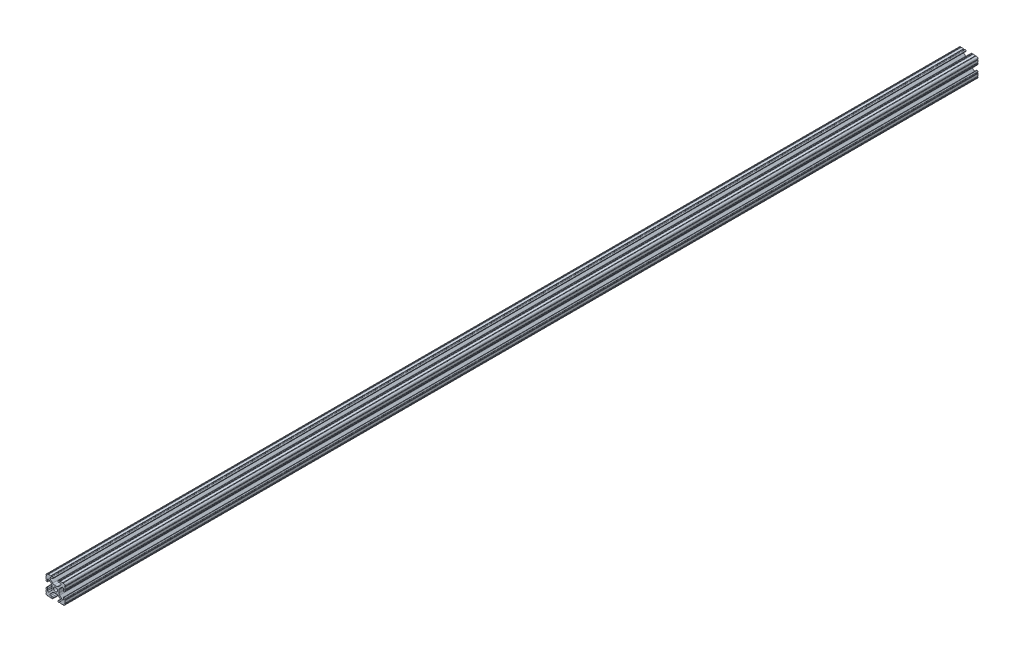
SolidWorks part; units mm, degrees
ref_plane "Front Plane" through (0, 0, 0) normal (0, 0, 1) x (1, 0, 0)
ref_plane "Top Plane" through (0, 0, 0) normal (0, 1, 0) x (1, 0, 0)
ref_plane "Right Plane" through (0, 0, 0) normal (1, 0, 0) x (0, 0, -1)
sketch "Sketch1" plane through (0, 0, 0) normal (0, 0, 1) x (1, 0, 0)
  line L88 (-7.1797, -8.6452) -> (-3.9523, -5.4237)
  line L89 (-1.7093, -4.4958) -> (1.7093, -4.4958)
  line L90 (3.9523, -5.4237) -> (7.1797, -8.6452)
  line L91 (6.4164, -10.4902) -> (4.2875, -10.4902)
  line L92 (3.2385, -11.5392) -> (3.2385, -11.651)
  line L93 (4.2875, -12.7) -> (5.3171, -12.7)
  line L94 (6.3331, -12.7) -> (9.5504, -12.7)
  line L95 (12.7, -9.5504) -> (12.7, -6.3331)
  line L96 (12.7, -5.3171) -> (12.7, -4.2875)
  line L97 (11.651, -3.2385) -> (11.5392, -3.2385)
  line L98 (10.4902, -4.2875) -> (10.4902, -6.4021)
  line L99 (8.7371, -7.1294) -> (5.441, -3.8408)
  line L100 (4.5085, -1.5932) -> (4.5085, 1.5932)
  line L101 (5.441, 3.8408) -> (8.7371, 7.1294)
  line L102 (10.4902, 6.4021) -> (10.4902, 4.2875)
  line L103 (11.5392, 3.2385) -> (11.651, 3.2385)
  line L104 (12.7, 4.2875) -> (12.7, 5.3171)
  line L105 (12.7, 6.3331) -> (12.7, 9.5504)
  line L106 (9.5504, 12.7) -> (6.3331, 12.7)
  line L107 (5.3171, 12.7) -> (4.2875, 12.7)
  line L108 (3.2385, 11.651) -> (3.2385, 11.5392)
  line L109 (4.2875, 10.4902) -> (6.4768, 10.4902)
  line L110 (7.207, 8.7244) -> (3.8983, 5.4232)
  line L111 (1.6558, 4.4958) -> (-1.6558, 4.4958)
  line L112 (-3.8983, 5.4232) -> (-7.207, 8.7244)
  line L113 (-6.4768, 10.4902) -> (-4.2875, 10.4902)
  line L114 (-3.2385, 11.5392) -> (-3.2385, 11.651)
  line L115 (-4.2875, 12.7) -> (-5.3171, 12.7)
  line L116 (-6.3331, 12.7) -> (-9.5504, 12.7)
  line L117 (-12.7, 9.5504) -> (-12.7, 6.3331)
  line L118 (-12.7, 5.3171) -> (-12.7, 4.2875)
  line L119 (-11.651, 3.2385) -> (-11.5392, 3.2385)
  line L120 (-10.4902, 4.2875) -> (-10.4902, 6.4021)
  line L121 (-8.7371, 7.1294) -> (-5.441, 3.8408)
  line L122 (-4.5085, 1.5932) -> (-4.5085, -1.5932)
  line L123 (-5.441, -3.8408) -> (-8.7371, -7.1294)
  line L124 (-10.4902, -6.4021) -> (-10.4902, -4.2875)
  line L125 (-11.5392, -3.2385) -> (-11.651, -3.2385)
  line L126 (-12.7, -4.2875) -> (-12.7, -5.3171)
  line L127 (-12.7, -6.3331) -> (-12.7, -9.5504)
  line L128 (-9.5504, -12.7) -> (-6.3331, -12.7)
  line L129 (-5.3171, -12.7) -> (-4.2875, -12.7)
  line L130 (-3.2385, -11.651) -> (-3.2385, -11.5392)
  line L131 (-4.2875, -10.4902) -> (-6.4164, -10.4902)
  circle A1 centre (0, 0) radius 2.6035
  arc A104 (-7.1797, -8.6452) -> (-6.4164, -10.4902) centre (-6.4164, -9.4098) ccw
  arc A105 (-1.7093, -4.4958) -> (-3.9523, -5.4237) centre (-1.7093, -7.6708) ccw
  arc A106 (3.9523, -5.4237) -> (1.7093, -4.4958) centre (1.7093, -7.6708) ccw
  arc A107 (6.4164, -10.4902) -> (7.1797, -8.6452) centre (6.4164, -9.4098) ccw
  arc A108 (4.2875, -10.4902) -> (3.2385, -11.5392) centre (4.2875, -11.5392) ccw
  arc A109 (3.2385, -11.651) -> (4.2875, -12.7) centre (4.2875, -11.651) ccw
  arc A110 (6.3331, -12.7) -> (5.3171, -12.7) centre (5.8251, -12.7) ccw
  arc A111 (10.5664, -12.6998) -> (9.5504, -12.7) centre (10.0584, -12.7) ccw
  arc A112 (10.5664, -12.6998) -> (12.6998, -10.5664) centre (10.5918, -10.5918) ccw
  arc A113 (12.7, -9.5504) -> (12.6998, -10.5664) centre (12.7, -10.0584) ccw
  arc A114 (12.7, -5.3171) -> (12.7, -6.3331) centre (12.7, -5.8251) ccw
  arc A115 (12.7, -4.2875) -> (11.651, -3.2385) centre (11.651, -4.2875) ccw
  arc A116 (11.5392, -3.2385) -> (10.4902, -4.2875) centre (11.5392, -4.2875) ccw
  arc A117 (8.7371, -7.1294) -> (10.4902, -6.4021) centre (9.4628, -6.4021) ccw
  arc A118 (4.5085, -1.5932) -> (5.441, -3.8408) centre (7.6835, -1.5932) ccw
  arc A119 (5.441, 3.8408) -> (4.5085, 1.5932) centre (7.6835, 1.5932) ccw
  arc A120 (10.4902, 6.4021) -> (8.7371, 7.1294) centre (9.4628, 6.4021) ccw
  arc A121 (10.4902, 4.2875) -> (11.5392, 3.2385) centre (11.5392, 4.2875) ccw
  arc A122 (11.651, 3.2385) -> (12.7, 4.2875) centre (11.651, 4.2875) ccw
  arc A123 (12.7, 6.3331) -> (12.7, 5.3171) centre (12.7, 5.8251) ccw
  arc A124 (12.6998, 10.5664) -> (12.7, 9.5504) centre (12.7, 10.0584) ccw
  arc A125 (12.6998, 10.5664) -> (10.5664, 12.6998) centre (10.5918, 10.5918) ccw
  arc A126 (9.5504, 12.7) -> (10.5664, 12.6998) centre (10.0584, 12.7) ccw
  arc A127 (5.3171, 12.7) -> (6.3331, 12.7) centre (5.8251, 12.7) ccw
  arc A128 (4.2875, 12.7) -> (3.2385, 11.651) centre (4.2875, 11.651) ccw
  arc A129 (3.2385, 11.5392) -> (4.2875, 10.4902) centre (4.2875, 11.5392) ccw
  arc A130 (7.207, 8.7244) -> (6.4768, 10.4902) centre (6.4768, 9.4563) ccw
  arc A131 (1.6558, 4.4958) -> (3.8983, 5.4232) centre (1.6558, 7.6708) ccw
  arc A132 (-3.8983, 5.4232) -> (-1.6558, 4.4958) centre (-1.6558, 7.6708) ccw
  arc A133 (-6.4768, 10.4902) -> (-7.207, 8.7244) centre (-6.4768, 9.4563) ccw
  arc A134 (-4.2875, 10.4902) -> (-3.2385, 11.5392) centre (-4.2875, 11.5392) ccw
  arc A135 (-3.2385, 11.651) -> (-4.2875, 12.7) centre (-4.2875, 11.651) ccw
  arc A136 (-6.3331, 12.7) -> (-5.3171, 12.7) centre (-5.8251, 12.7) ccw
  arc A137 (-10.5664, 12.6998) -> (-9.5504, 12.7) centre (-10.0584, 12.7) ccw
  arc A138 (-10.5664, 12.6998) -> (-12.6998, 10.5664) centre (-10.5918, 10.5918) ccw
  arc A139 (-12.7, 9.5504) -> (-12.6998, 10.5664) centre (-12.7, 10.0584) ccw
  arc A140 (-12.7, 5.3171) -> (-12.7, 6.3331) centre (-12.7, 5.8251) ccw
  arc A141 (-12.7, 4.2875) -> (-11.651, 3.2385) centre (-11.651, 4.2875) ccw
  arc A142 (-11.5392, 3.2385) -> (-10.4902, 4.2875) centre (-11.5392, 4.2875) ccw
  arc A143 (-8.7371, 7.1294) -> (-10.4902, 6.4021) centre (-9.4628, 6.4021) ccw
  arc A144 (-4.5085, 1.5932) -> (-5.441, 3.8408) centre (-7.6835, 1.5932) ccw
  arc A145 (-5.441, -3.8408) -> (-4.5085, -1.5932) centre (-7.6835, -1.5932) ccw
  arc A146 (-10.4902, -6.4021) -> (-8.7371, -7.1294) centre (-9.4628, -6.4021) ccw
  arc A147 (-10.4902, -4.2875) -> (-11.5392, -3.2385) centre (-11.5392, -4.2875) ccw
  arc A148 (-11.651, -3.2385) -> (-12.7, -4.2875) centre (-11.651, -4.2875) ccw
  arc A149 (-12.7, -6.3331) -> (-12.7, -5.3171) centre (-12.7, -5.8251) ccw
  arc A150 (-12.6998, -10.5664) -> (-12.7, -9.5504) centre (-12.7, -10.0584) ccw
  arc A151 (-12.6998, -10.5664) -> (-10.5664, -12.6998) centre (-10.5918, -10.5918) ccw
  arc A152 (-9.5504, -12.7) -> (-10.5664, -12.6998) centre (-10.0584, -12.7) ccw
  arc A153 (-5.3171, -12.7) -> (-6.3331, -12.7) centre (-5.8251, -12.7) ccw
  arc A154 (-4.2875, -12.7) -> (-3.2385, -11.651) centre (-4.2875, -11.651) ccw
  arc A155 (-3.2385, -11.5392) -> (-4.2875, -10.4902) centre (-4.2875, -11.5392) ccw
extrude "Boss-Extrude1" add sketch "Sketch1" along normal mid plane 1219.2
sketch "Sketch2" plane through (4.5085, 0, 0) normal (1, 0, 0) x (0, 0, -1)
  line L1 (0, 17.2111) -> (0, -17.5175) construction
  circle A0 centre (38.1, 0) radius 3.175
  circle A2 centre (-38.1, 0) radius 3.175
  circle A3 centre (0, 0) radius 3.175
  dimension "D1" = 6.35
  dimension "D2" = 38.1
  dimension "D3" = 6.35
  dimension "D4" = 6.35
  dimension "D6" = 76.2
extrude "Cut-Extrude1" cut sketch "Sketch2" against normal through all and the other way through all
